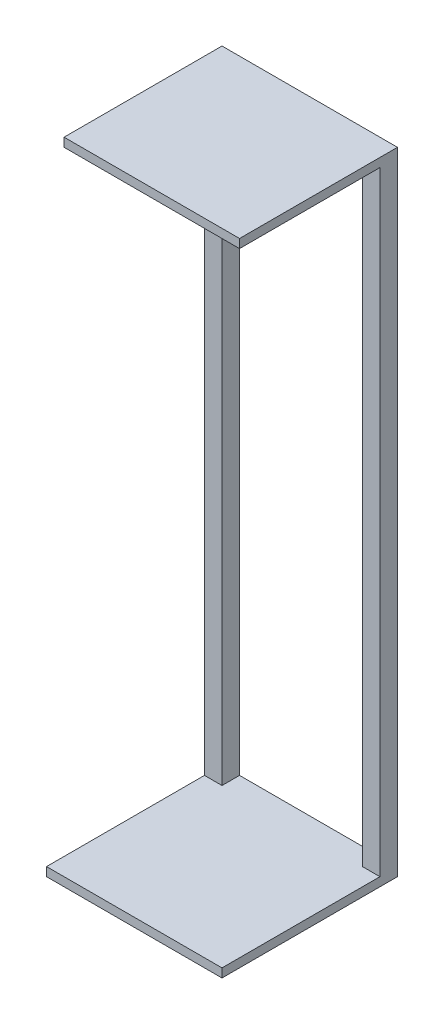
SolidWorks part; units mm, degrees
ref_plane "Front Plane" through (0, 0, 0) normal (0, 0, 1) x (1, 0, 0)
ref_plane "Top Plane" through (0, 0, 0) normal (0, 1, 0) x (1, 0, 0)
ref_plane "Right Plane" through (0, 0, 0) normal (1, 0, 0) x (0, 0, -1)
sketch "Sketch2" plane through (0, 0, 0) normal (0, 1, 0) x (1, 0, 0)
  line L1 (0, 0) -> (200, 0)
  line L2 (0, 0) -> (0, 200)
  line L3 (0, 200) -> (200, 200)
  line L4 (200, 0) -> (200, 200)
  dimension "D1" = 200
  dimension "D2" = 200
extrude "Boss-Extrude1" add sketch "Sketch2" along normal blind 10
sketch "Sketch3" plane through (0, 10, 0) normal (0, 1, 0) x (1, 0, 0)
  line L0 (0, -55) -> (0, 55) construction
  line L1 (200, 200) -> (180, 200)
  line L2 (200, 200) -> (200, 180)
  line L3 (200, 180) -> (180, 180)
  line L4 (180, 200) -> (180, 180)
  line L5 (200, 200) -> (0, 200) construction
  line L7 (0, 200) -> (20, 200)
  line L8 (0, 200) -> (0, 180)
  line L9 (0, 180) -> (20, 180)
  line L10 (20, 200) -> (20, 180)
  point P5 (0, 200)
  dimension "D1" = 20
  dimension "D2" = 20
  dimension "D3" = 20
  dimension "D4" = 20
extrude "Boss-Extrude2" add sketch "Sketch3" along normal blind 700
sketch "Sketch4" plane through (0, 710, 0) normal (0, 1, 0) x (1, 0, 0)
  line L0 (0, -110) -> (0, 110) construction
  line L1 (200, 200) -> (0, 200)
  line L2 (200, 200) -> (200, 20)
  line L3 (200, 20) -> (0, 20)
  line L4 (0, 200) -> (0, 20)
  dimension "D1" = 180
extrude "Boss-Extrude3" add sketch "Sketch4" along normal blind 10
sketch "Sketch5" plane through (0, 710, 0) normal (0, -1, 0) x (1, 0, 0)
  line L0 (100, -20) -> (100, -200) construction
  line L1 (0, -20) -> (200, -20) construction
  line L2 (180, -200) -> (20, -200) construction
  line L3 (0, -110) -> (200, -110)
  line L4 (200, -20) -> (200, -180) construction
  line L5 (0, -100) -> (200, -100) construction
  line L6 (0, -180) -> (0, -20) construction
  line L8 (80, -100) -> (120, -100)
  line L9 (80, -100) -> (80, -120)
  line L10 (80, -120) -> (120, -120)
  line L11 (120, -100) -> (120, -120)
  line L12 (80, -100) -> (120, -120) construction
  line L13 (80, -120) -> (120, -100) construction
  point P11 (100, -110)
  point P15 (100, -110)
  dimension "D1" = 40
  dimension "D2" = 20
extrude "Boss-Extrude4" add sketch "Sketch5" along normal blind 20 contours L11 L8 L9 L3 | L11 L3 L9 L10 region at (100, 710, -105) region at (100, 710, -115)
sketch "Sketch7" plane through (120, 0, 0) normal (1, 0, 0) x (0, 0, -1)
  line L0 (110, 690) -> (110, 710) construction
  line L1 (100, 690) -> (120, 690) construction
  line L2 (20, 710) -> (180, 710) construction
  circle A0 centre (110, 690) radius 10
extrude "Boss-Extrude7" add sketch "Sketch7" against normal up to surface (40 mm away) contours A0 up to face at (80, 700, -110)
sketch "Sketch10" plane through (0, 0, -100) normal (0, 0, 1) x (1, 0, 0)
  line L0 (80, 710) -> (120, 710) construction
  line L1 (85, 710) -> (115, 710)
  line L2 (85, 710) -> (85, 669.7183)
  line L3 (85, 669.7183) -> (115, 669.7183)
  line L4 (115, 710) -> (115, 669.7183)
  line L5 (80, 690) -> (80, 710) construction
  line L6 (120, 690) -> (120, 710) construction
  dimension "D1" = 5
  dimension "D2" = 5
extrude "Cut-Extrude2" cut sketch "Sketch10" against normal through all
sketch "Sketch11" plane through (120, 0, 0) normal (1, 0, 0) x (0, 0, -1)
  line L0 (100, 690) -> (120, 690) construction
  circle A0 centre (110, 690) radius 5
extrude "Boss-Extrude9" add sketch "Sketch11" against normal up to surface (40 mm away) up to face at (80, 697.5, -110)
